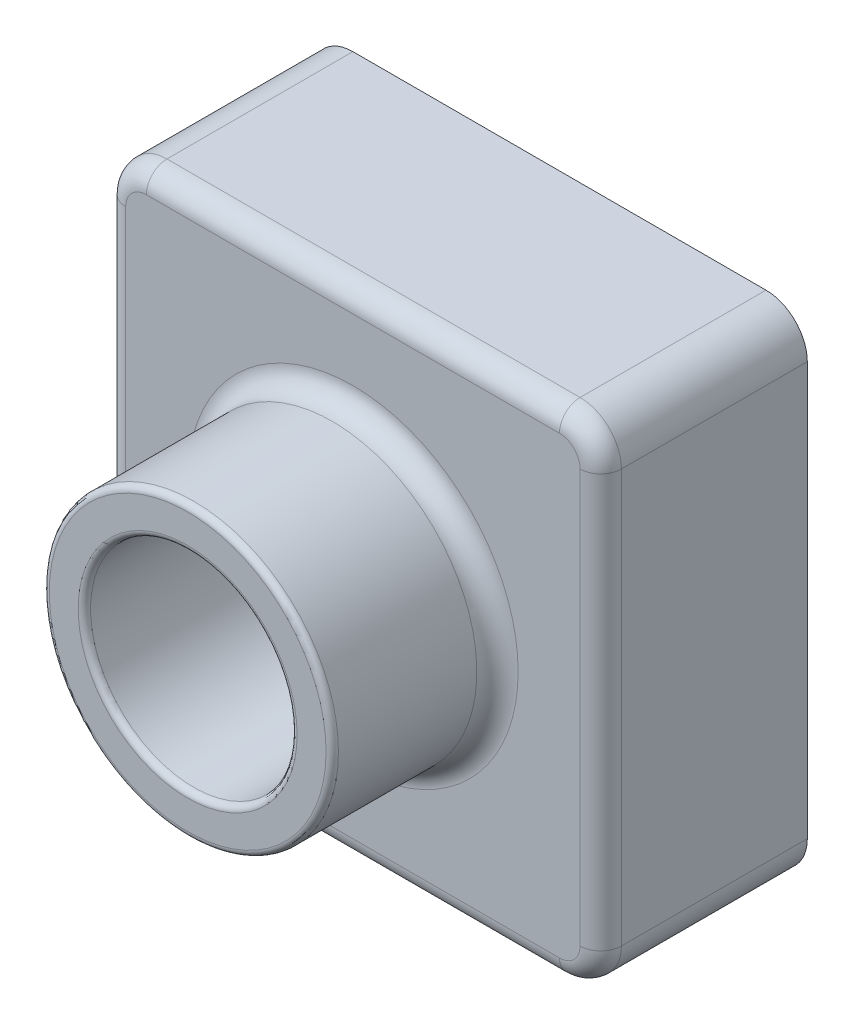
SolidWorks part; units mm, degrees
ref_plane "Front Plane" through (0, 0, 0) normal (0, 0, 1) x (1, 0, 0)
ref_plane "Top Plane" through (0, 0, 0) normal (0, 1, 0) x (1, 0, 0)
ref_plane "Right Plane" through (0, 0, 0) normal (1, 0, 0) x (0, 0, -1)
sketch "Sketch1" plane through (0, 0, 0) normal (0, 0, 1) x (1, 0, 0)
  line L5 (0, 0) -> (120, 0)
  line L6 (0, 0) -> (0, 120)
  line L7 (0, 120) -> (120, 120)
  line L8 (120, 0) -> (120, 120)
  dimension "D1" = 120
  dimension "D2" = 120
extrude "Boss-Extrude1" add sketch "Sketch1" along normal blind 50
sketch "Sketch3" plane through (0, 0, 50) normal (0, 0, 1) x (1, 0, 0)
  line L0 (120, 120) -> (0, 120) construction
  line L1 (120, 0) -> (120, 120) construction
  circle A1 centre (60, 60) radius 35
  dimension "D1" = 70
  dimension "D2" = 60
  dimension "D3" = 60
extrude "Boss-Extrude2" add sketch "Sketch3" along normal blind 40
sketch "Sketch4" plane through (0, 0, 90) normal (0, 0, 1) x (1, 0, 0)
  circle A0 centre (60, 60) radius 25
  dimension "D1" = 50
extrude "Cut-Extrude1" cut sketch "Sketch4" against normal through all
fillet "Fillet1" radius 10 4 edges at (0, 0, 25) (0, 120, 25) (120, 0, 25) (120, 120, 25)
fillet "Fillet2" radius 1.5 2 edges at (95, 60, 90) (85, 60, 90)
fillet "Fillet5" radius 5 9 edges at (117.0711, 2.9289, 50) (60, 0, 50) (2.9289, 2.9289, 50) (0, 60, 50) (2.9289, 117.0711, 50) (60, 120, 50) (117.0711, 117.0711, 50) (120, 60, 50) (95, 60, 50)
shell "Shell1" thickness 2 removed face at (85, 60, 0)
